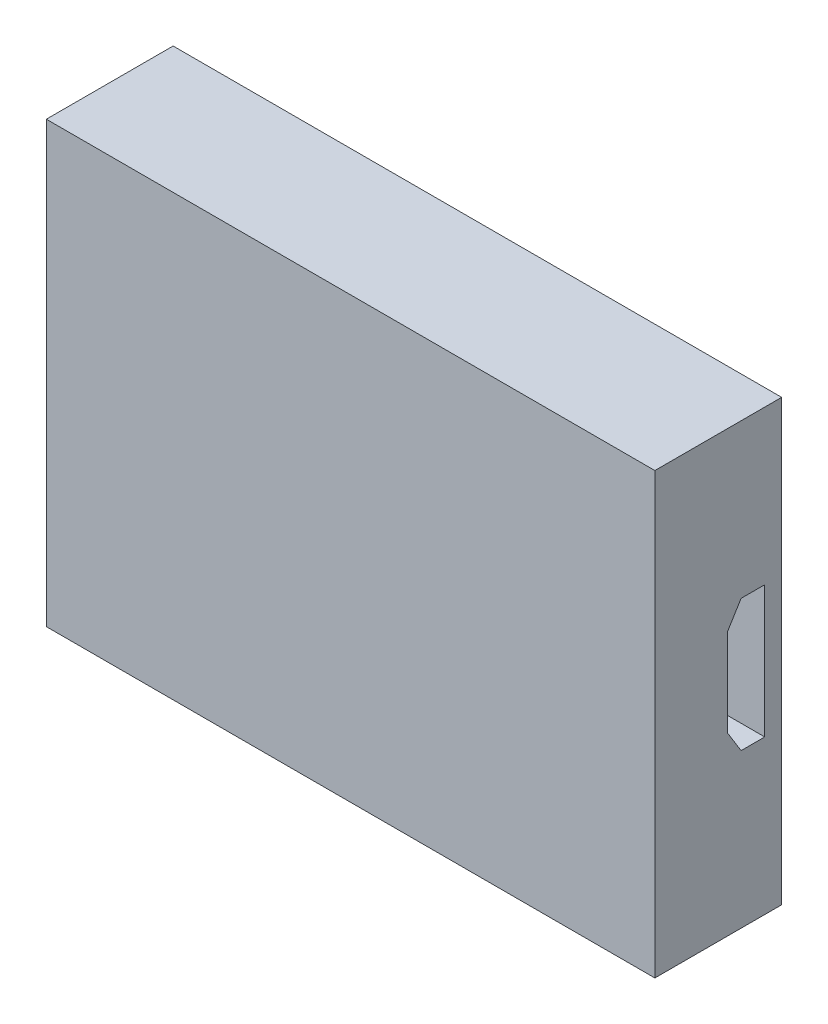
SolidWorks part; units mm, degrees
note: The reader was unsure of these and kept them because the rebuilt part matched: shared geometry of "Sketch1<4>".
ref_plane "Front Plane" through (0, 0, 0) normal (0, 0, 1) x (1, 0, 0)
ref_plane "Top Plane" through (0, 0, 0) normal (0, 1, 0) x (1, 0, 0)
ref_plane "Right Plane" through (0, 0, 0) normal (1, 0, 0) x (0, 0, -1)
sketch "Sketch1" plane through (0, 0, 0) normal (0, 0, 1) x (1, 0, 0)
  line L0 (13.75, 8.6) -> (13.75, -8.6) construction
  line L1 (13.75, 10) -> (-16.25, 10)
  line L2 (13.75, 10) -> (13.75, -10)
  line L3 (13.75, -10) -> (-16.25, -10)
  line L4 (-16.25, 10) -> (-16.25, -10)
  line L5 (13.75, 10) -> (-16.25, -10) construction
  line L6 (13.75, -10) -> (-16.25, 10) construction
  line L7 (16.75, 13) -> (16.75, -13)
  line L8 (16.75, -13) -> (-19.25, -13)
  line L9 (-19.25, 13) -> (-19.25, -13)
  line L10 (16.75, 13) -> (-19.25, 13)
  point P0 (0, 0)
  dimension "D1" = 30
  dimension "D2" = 20
  dimension "D3" = 3
extrude "Extrude-Thin1" add sketch "Sketch1" against normal blind 5.5 thin contours L1 L4 L3 L2
sketch "Sketch2" plane through (16.75, 0, 0) normal (1, 0, 0) x (0, 0, -1)
  line L0 (0, 13) -> (0, -13) construction
  line L5 (0, 0) -> (7, 0) construction
  line L6 (4.5, -3.9) -> (4.5, 3.9)
  line L7 (4.5, -3.9) -> (3.1, -3.9)
  line L8 (3.1, -3.9) -> (2.3, -2.6)
  line L9 (2.3, -2.6) -> (2.3, 0)
  line L10 (7, -13) -> (7, 13) construction
  line L11 (2.3, 2.6) -> (2.3, 0)
  line L12 (3.1, 3.9) -> (2.3, 2.6)
  line L13 (4.5, 3.9) -> (3.1, 3.9)
  point P1 (2.3, -1.3)
  point P7 (2.3, 1.3)
  point P14 (4.5, 0)
  dimension "D1" = 3.9
  dimension "D2" = 2.2
  dimension "D3" = 1.4
  dimension "D4" = 1.3
  dimension "D5" = 2.3
extrude "Cut-Extrude1" cut sketch "Sketch2" against normal up to next
extrude "Boss-Extrude3" add sketch "Sketch1<4>" along normal blind 2 contours L1 L4 L3 L2 | L7 L10 L9 L8 L4 L1 L2 L3
sketch "Sketch1<4>" plane through (0, 0, 0) normal (0, 0, 1) x (1, 0, 0) same geometry as "Sketch1"
sketch "Sketch4" plane through (0, 0, -5.5) normal (0, 0, -1) x (-1, 0, 0)
  line L0 (-16.75, 13) -> (19.25, 13) construction
  line L1 (-16.75, 13) -> (-16.75, -13) construction
  line L2 (-14.75, 11) -> (17.25, 11) construction
  circle A0 centre (-14.75, 11) radius 0.9
  circle A1 centre (17.25, 11) radius 0.9
  circle A2 centre (17.25, -11) radius 0.9
  circle A3 centre (-14.75, -11) radius 0.9
  dimension "D1" = 1.8
  dimension "D2" = 2
  dimension "D3" = 2
  dimension "D6" = 32
  dimension "D4" = 2
  dimension "D5" = 2
extrude "Cut-Extrude4" cut sketch "Sketch4" against normal blind 5
sketch "Sketch5" plane through (-19.25, 0, 0) normal (-1, 0, 0) x (0, 0, 1)
  line L1 (-5.5, 0) -> (2, 0) construction
  line L2 (-5.5, 13) -> (-5.5, -13) construction
  line L3 (2, 13) -> (2, -13) construction
  circle A0 centre (-2.5, 4.2) radius 0.5
  circle A1 centre (-2.5, -4.2) radius 0.5
  dimension "D1" = 4.2
  dimension "D2" = 1
  dimension "D3" = 4.5
extrude "Cut-Extrude5" cut sketch "Sketch5" against normal up to next
